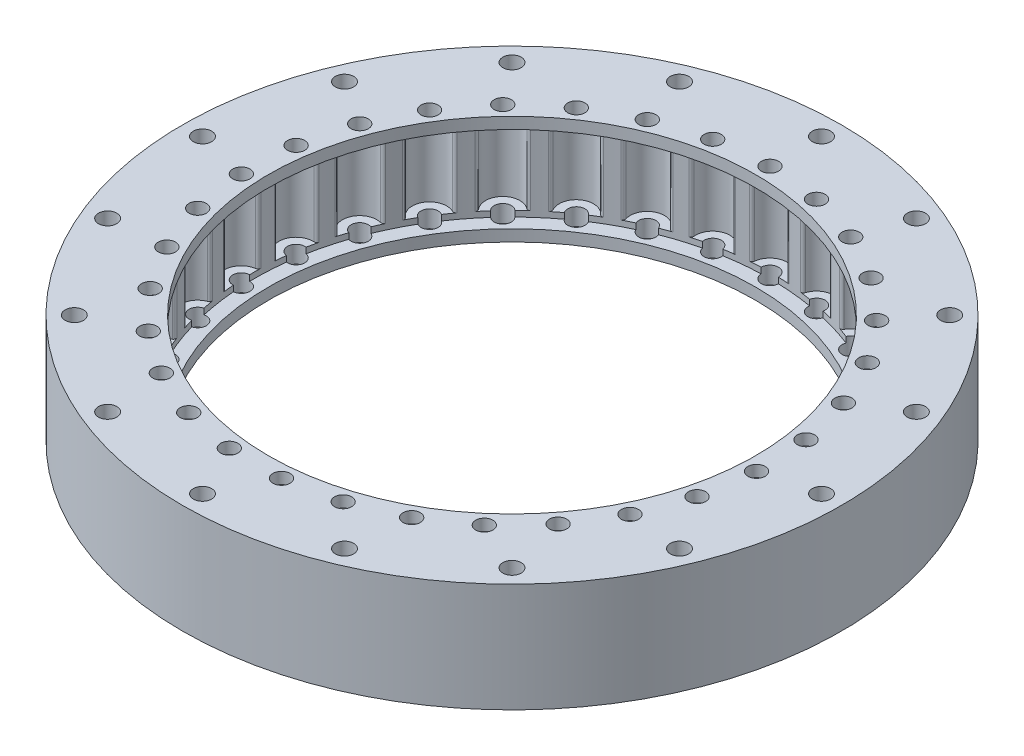
SolidWorks part; units mm, degrees
ref_plane "Front Plane" through (0, 0, 0) normal (0, 0, 1) x (1, 0, 0)
ref_plane "Top Plane" through (0, 0, 0) normal (0, 1, 0) x (1, 0, 0)
ref_plane "Right Plane" through (0, 0, 0) normal (1, 0, 0) x (0, 0, -1)
sketch "Sketch1" plane through (0, 0, 0) normal (0, 1, 0) x (1, 0, 0)
  line L0 (15.8389, 51.6249) -> (0, 0) construction
  line L1 (0, 0) -> (-4.5526, -44.7691) construction
  circle A0 centre (0, 0) radius 45
  circle A12 centre (0, 0) radius 57.5
  circle A13 centre (0, 0) radius 54 construction
  point P27 (0, 0)
  point P54 (0, 0)
  dimension "D1" = 90
  dimension "D4" = 115
  dimension "D5" = 108
  dimension "D8" = 11.25
extrude "Boss-Extrude1" add sketch "Sketch1" along normal blind 13 contours A12 region at (-55.8737, 0, 0)
sketch "Sketch2" plane through (0, 0, 0) normal (0, -1, 0) x (1, 0, 0)
  circle A0 centre (0, 0) radius 57.5
  circle A1 centre (0, 0) radius 45
extrude "Boss-Extrude2" add sketch "Sketch2" along normal blind 1
sketch "Sketch3" plane through (0, -1, 0) normal (0, -1, 0) x (1, 0, 0)
  circle A0 centre (0, 0) radius 57.5
  circle A1 centre (0, 0) radius 42.5
  dimension "D1" = 85
extrude "Boss-Extrude3" add sketch "Sketch3" along normal blind 2
sketch "Sketch5" plane through (0, 13, 0) normal (0, 1, 0) x (1, 0, 0)
  circle A0 centre (0, 45) radius 3
  circle A1 centre (0, 0) radius 45 construction
  circle A2 centre (0, 0) radius 45 construction
  dimension "D1" = 6
extrude "Cut-Extrude2" cut sketch "Sketch5" against normal blind 13
fillet "Fillet4" radius 0.5 2 edges at (2.9983, 6.5, -44.9) (-2.9983, 6.5, -44.9)
sketch "Sketch10" plane through (0, 13, 0) normal (0, 1, 0) x (1, 0, 0)
  circle A0 centre (0, 0) radius 45
  circle A1 centre (0, 0) radius 57.5
extrude "Boss-Extrude4" add sketch "Sketch10" along normal blind 1
sketch "Sketch11" plane through (0, 14, 0) normal (0, 1, 0) x (1, 0, 0)
  circle A0 centre (0, 0) radius 42.5
  circle A1 centre (0, 0) radius 57.5
extrude "Boss-Extrude5" add sketch "Sketch11" along normal blind 2
sketch "Sketch7" plane through (0, 16, 0) normal (0, 1, 0) x (1, 0, 0)
  circle A0 centre (0, 45) radius 1.5
  arc A1 (3.4425, 44.8681) -> (-3.4425, 44.8681) centre (0, 0) ccw construction
  dimension "D1" = 3
extrude "Cut-Extrude3" cut sketch "Sketch7" against normal blind 23
pattern_circular "CirPattern3" count 31 over 360 about axis through (0, -3, 0) along (0, 1, 0) of "Cut-Extrude2", "Fillet4", "Cut-Extrude3"
sketch "Sketch4" plane through (0, 16, 0) normal (0, 1, 0) x (1, 0, 0)
  circle A0 centre (0, 0) radius 54 construction
  circle A1 centre (0, 54) radius 1.6
  circle A2 centre (20.6649, 49.8895) radius 1.6
  circle A3 centre (38.1838, 38.1838) radius 1.6
  circle A4 centre (49.8895, 20.6649) radius 1.6
  circle A5 centre (54, 0) radius 1.6
  circle A6 centre (49.8895, -20.6649) radius 1.6
  circle A7 centre (38.1838, -38.1838) radius 1.6
  circle A8 centre (20.6649, -49.8895) radius 1.6
  circle A9 centre (0, -54) radius 1.6
  circle A10 centre (-20.6649, -49.8895) radius 1.6
  circle A11 centre (-38.1838, -38.1838) radius 1.6
  circle A12 centre (-49.8895, -20.6649) radius 1.6
  circle A13 centre (-54, 0) radius 1.6
  circle A14 centre (-49.8895, 20.6649) radius 1.6
  circle A15 centre (-38.1838, 38.1838) radius 1.6
  circle A16 centre (-20.6649, 49.8895) radius 1.6
  circle A17 centre (0, 0) radius 45 construction
  point P38 (0, 0)
  point P102 (0, 0)
  dimension "D1" = 108
  dimension "D2" = 3.2
extrude "Cut-Extrude1" cut sketch "Sketch4" against normal blind 51
